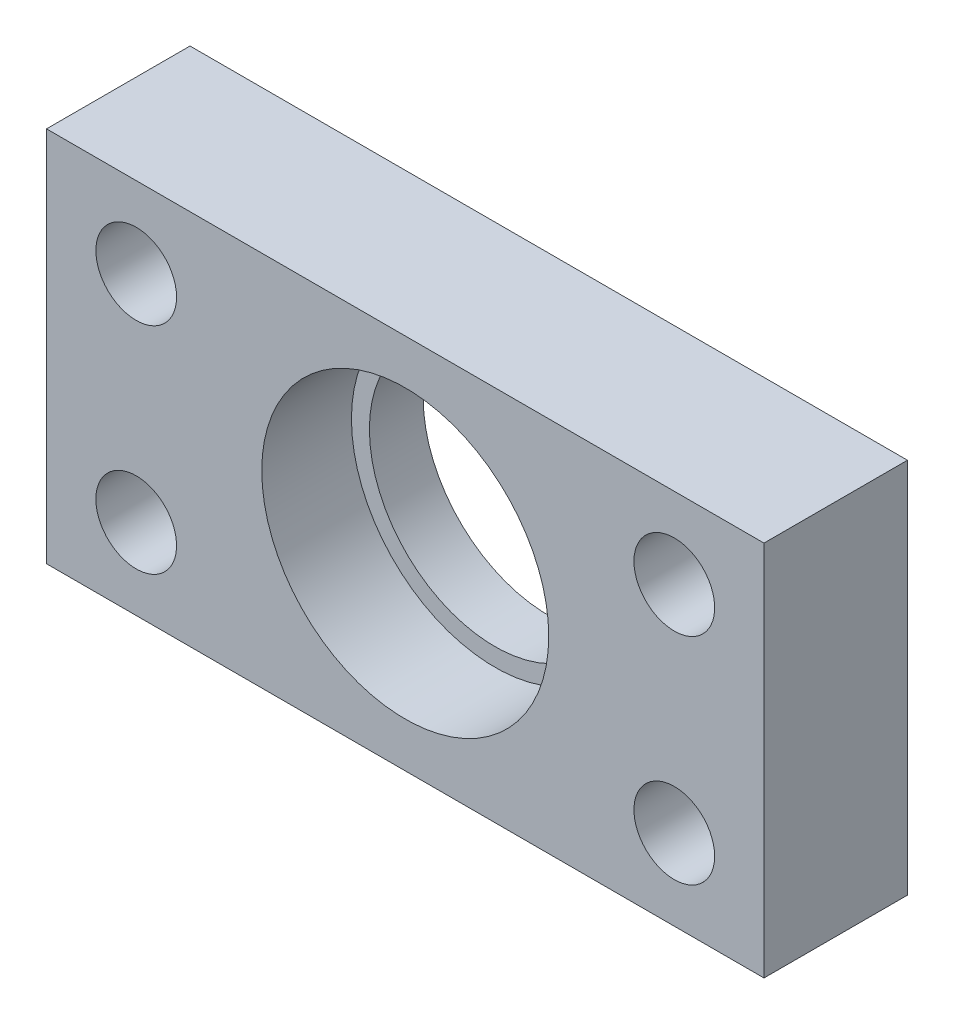
SolidWorks part; units mm, degrees
ref_plane "Front" through (0, 0, 0) normal (0, 0, 1) x (1, 0, 0)
ref_plane "Top" through (0, 0, 0) normal (0, 1, 0) x (1, 0, 0)
ref_plane "Right" through (0, 0, 0) normal (1, 0, 0) x (0, 0, -1)
sketch "Esquisse1" plane through (0, 0, 0) normal (0, 0, 1) x (1, 0, 0)
  line L1 (0, 0) -> (40, 0)
  line L2 (0, 0) -> (0, 21)
  line L3 (0, 21) -> (40, 21)
  line L4 (40, 0) -> (40, 21)
  dimension "D1" = 40
  dimension "D2" = 21
extrude "Boss.-Extru.1" add sketch "Esquisse1" along normal blind 8
sketch "Esquisse2" plane through (0, 0, 8) normal (0, 0, 1) x (1, 0, 0)
  line L0 (0, 10.5) -> (40, 10.5) construction
  line L1 (0, 21) -> (0, 0) construction
  line L2 (40, 0) -> (40, 21) construction
  circle A0 centre (20, 10.5) radius 8
  dimension "D1" = 16
extrude "Enlèv. mat.-Extru.1" cut sketch "Esquisse2" against normal blind 5
sketch "Esquisse3" plane through (0, 0, 3) normal (0, 0, 1) x (1, 0, 0)
  circle A0 centre (20, 10.5) radius 7
  dimension "D1" = 14
extrude "Enlèv. mat.-Extru.2" cut sketch "Esquisse3" against normal through all
sketch "Esquisse5" plane through (0, 0, 8) normal (0, 0, 1) x (1, 0, 0)
  line L0 (5, 0) -> (5, 21) construction
  line L1 (0, 0) -> (40, 0) construction
  line L2 (40, 21) -> (0, 21) construction
  line L3 (0, 10.5) -> (40, 10.5) construction
  line L4 (0, 21) -> (0, 0) construction
  line L5 (40, 0) -> (40, 21) construction
  line L6 (20, 10.5) -> (20, 21) construction
  line L7 (35, 0) -> (35, 21) construction
  circle A0 centre (5, 16.5) radius 2.25
  circle A1 centre (5, 4.5) radius 2.25
  circle A2 centre (35, 4.5) radius 2.25
  circle A3 centre (35, 16.5) radius 2.25
  dimension "D1" = 4.5
  dimension "D2" = 12
  dimension "D3" = 30
extrude "Enlèv. mat.-Extru.4" cut sketch "Esquisse5" against normal through all
